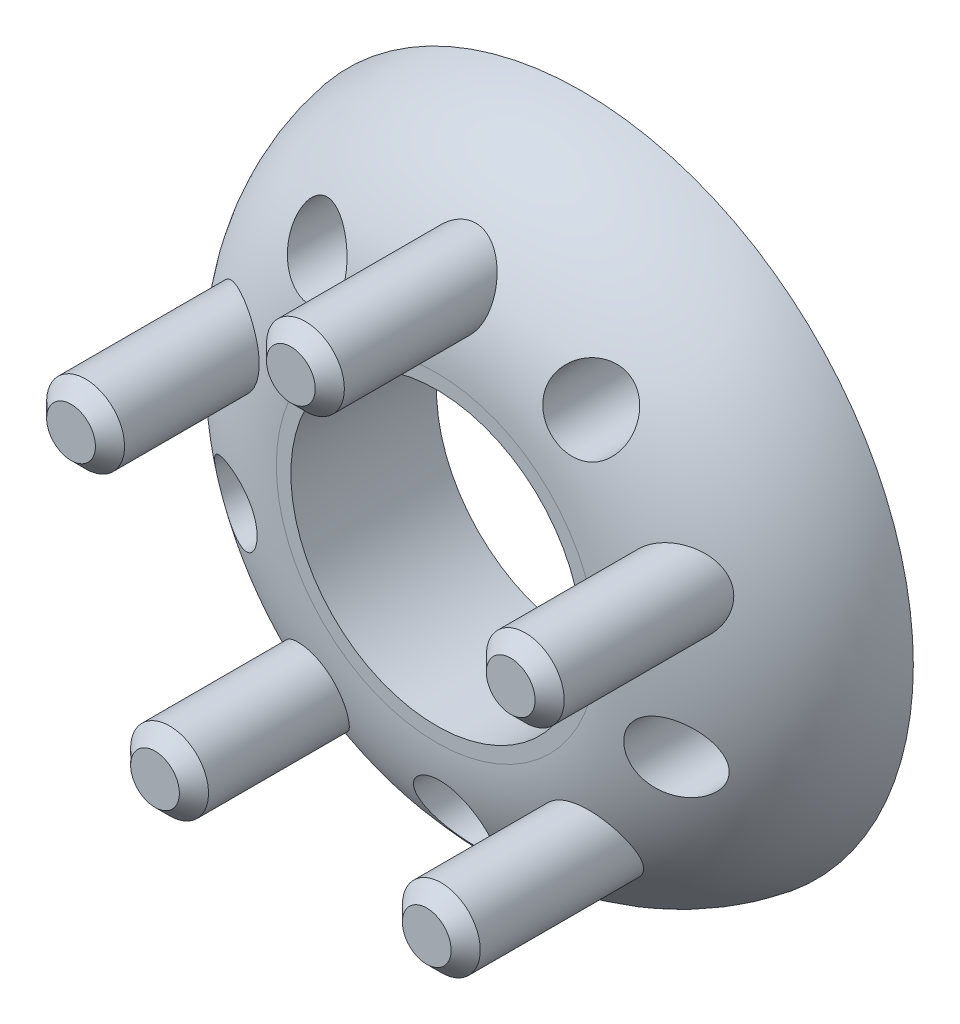
SolidWorks part; units mm, degrees
material "ABS"
ref_plane "Front Plane" through (0, 0, 0) normal (0, 0, 1) x (1, 0, 0)
ref_plane "Top Plane" through (0, 0, 0) normal (0, 1, 0) x (1, 0, 0)
ref_plane "Right Plane" through (0, 0, 0) normal (1, 0, 0) x (0, 0, -1)
sketch "스케치2" plane through (0, 0, 0) normal (1, 0, 0) x (0, 0, -1)
  line L1 (0, 0) -> (0, 11)
  line L2 (10, 22.7515) -> (10, 0)
  line L4 (10, 0) -> (0, 0) construction
  line L5 (0, 0) -> (10, 0)
  line L6 (7.5, 0) -> (7.5, 22.06) construction
  arc A2 (10, 22.7515) -> (0, 11) centre (11.9049, 11) ccw
  dimension "D3" = 11.9049
  dimension "D1" = 10
  dimension "D2" = 7.5
  dimension "D5" = 11
revolve "회전1" add sketch "스케치2" angle 360 about L4
sketch "Sketch8" plane through (0, 0, -10) normal (0, 0, -1) x (-1, 0, 0)
  line L10 (0, 15.875) -> (0, 0) construction
  circle A0 centre (0, 0) radius 13.2 construction
  circle A1 centre (0, 0) radius 18.55 construction
  circle A2 centre (0, 15.875) radius 2.675
  dimension "D1" = 26.4
  dimension "D2" = 37.1
extrude "Boss-Extrude3" add sketch "Sketch8" against normal offset from surface (20 mm away) 10 up to plane "Front Plane" offset beyond the face yes
sketch "Sketch9" plane through (0, 0, 10) normal (0, 0, 1) x (1, 0, 0)
  line L0 (0, 0) -> (-50000, 0) construction
  line L1 (0, 15.875) -> (0, 0) construction
  line L2 (0, 15.875) -> (0, -15.875) construction
  circle A2 centre (0, -15.875) radius 2.5
  dimension "D1" = 5
chamfer "Chamfer1" distance 1 angle 45 1 edges at (2.675, 15.875, 10)
extrude "컷-돌출2" cut sketch "Sketch9" against normal through all
sketch "스케치3" plane through (0, 0, 0) normal (0, 0, 1) x (1, 0, 0)
  circle A0 centre (0, 0) radius 10
  dimension "D1" = 20
extrude "컷-돌출3" cut sketch "스케치3" against normal through all
pattern_circular "원형 패턴2" count 5 over 360 about axis through (0, 0, -10) along (0, 0, 1) of "컷-돌출2", "Chamfer1", "Boss-Extrude3"
